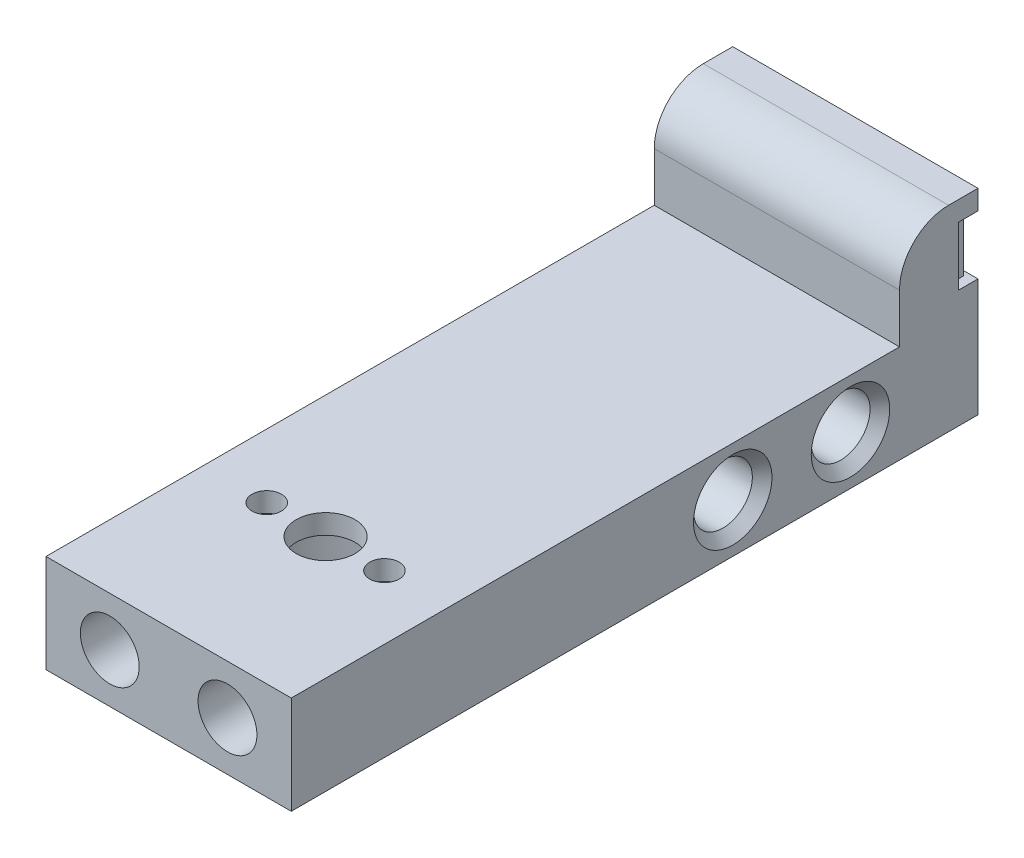
SolidWorks part; units mm, degrees
ref_plane "Front Plane" through (0, 0, 0) normal (0, 0, 1) x (1, 0, 0)
ref_plane "Top Plane" through (0, 0, 0) normal (0, 1, 0) x (1, 0, 0)
ref_plane "Right Plane" through (0, 0, 0) normal (1, 0, 0) x (0, 0, -1)
sketch "Sketch1" plane through (0, 0, 0) normal (0, 1, 0) x (1, 0, 0)
  line L1 (-12.5, 11) -> (12.5, 11)
  line L2 (-12.5, 11) -> (-12.5, -11)
  line L3 (-12.5, -11) -> (12.5, -11)
  line L4 (12.5, 11) -> (12.5, -11)
  line L5 (-12.5, 11) -> (12.5, -11) construction
  line L6 (-12.5, -11) -> (12.5, 11) construction
  point P0 (0, 0)
  dimension "D1" = 22
  dimension "D2" = 25
extrude "Boss-Extrude1" add sketch "Sketch1" along normal blind 10
sketch "Sketch2" plane through (12.5, 0, 0) normal (1, 0, 0) x (0, 0, -1)
  line L0 (-11, 10) -> (-11, 0) construction
  line L1 (-11, 0) -> (11, 0) construction
  line L2 (11, 10) -> (11, 0) construction
  circle A0 centre (-6, 5) radius 3
  circle A1 centre (6, 5) radius 3
  dimension "D1" = 5
  dimension "D3" = 5
  dimension "D2" = 5
extrude "Cut-Extrude1" cut sketch "Sketch2" against normal through all
chamfer "Chamfer1" distance 1 angle 45 4 edges at (-12.5, 5, -9) (-12.5, 5, 3) (12.5, 5, -9) (12.5, 5, 3)
sketch "Sketch3" plane through (0, 10, 0) normal (0, 1, 0) x (1, 0, 0)
  line L6 (-12.5, 11) -> (-12.5, 19)
  line L7 (-12.5, 19) -> (12.5, 19)
  line L8 (12.5, 19) -> (12.5, 11)
  line L9 (12.5, 11) -> (-12.5, 11)
  dimension "D2" = 8
extrude "Boss-Extrude4" add sketch "Sketch3" along normal blind 10 and the other way blind 10
sketch "Sketch5" plane through (0, 0, 11) normal (0, 0, 1) x (1, 0, 0)
  line L1 (-12.5, 10) -> (12.5, 10)
  line L2 (-12.5, 10) -> (-12.5, 0)
  line L3 (-12.5, 0) -> (12.5, 0)
  line L4 (12.5, 10) -> (12.5, 0)
ref_plane "Plane1" through (0, 18, 0) normal (0, 1, 0) x (1, 0, 0)
sketch "Sketch10" plane through (0, 18, 0) normal (0, 1, 0) x (1, 0, 0)
  line L0 (71.7878, 3.2338) -> (71.7878, 1.2338)
  line L1 (96.7878, 1.2338) -> (96.7878, 3.2338)
  line L2 (96.7878, 3.2338) -> (71.7878, 3.2338)
  line L3 (96.7878, 1.2338) -> (71.7878, 1.2338)
  line L4 (95.7878, 1.2338) -> (95.7878, 2.7338)
  line L5 (71.7878, 2.7338) -> (96.7878, 2.7338)
  line L6 (94.7878, 1.2338) -> (94.7878, 2.7338)
  line L7 (93.7878, 1.2338) -> (93.7878, 2.7338)
  line L8 (91.7878, 1.2338) -> (91.7878, 2.7338)
  line L9 (92.7878, 1.2338) -> (92.7878, 2.7338)
  line L10 (90.7878, 1.2338) -> (90.7878, 2.7338)
  line L11 (89.7878, 1.2338) -> (89.7878, 2.7338)
  line L12 (87.7878, 1.2338) -> (87.7878, 2.7338)
  line L13 (88.7878, 1.2338) -> (88.7878, 2.7338)
  line L14 (79.7878, 1.2338) -> (79.7878, 2.7338)
  line L15 (80.7878, 1.2338) -> (80.7878, 2.7338)
  line L16 (81.7878, 1.2338) -> (81.7878, 2.7338)
  line L17 (82.7878, 1.2338) -> (82.7878, 2.7338)
  line L18 (84.7878, 1.2338) -> (84.7878, 2.7338)
  line L19 (83.7878, 1.2338) -> (83.7878, 2.7338)
  line L20 (85.7878, 1.2338) -> (85.7878, 2.7338)
  line L21 (86.7878, 1.2338) -> (86.7878, 2.7338)
  line L22 (74.7878, 1.2338) -> (74.7878, 2.7338)
  line L23 (75.7878, 1.2338) -> (75.7878, 2.7338)
  line L24 (76.7878, 1.2338) -> (76.7878, 2.7338)
  line L25 (77.7878, 1.2338) -> (77.7878, 2.7338)
  line L26 (78.7878, 1.2338) -> (78.7878, 2.7338)
  line L27 (72.7878, 1.2338) -> (72.7878, 2.7338)
  line L28 (73.7878, 1.2338) -> (73.7878, 2.7338)
  line L29 (61.2878, 1) -> (61.2878, -1)
  line L30 (86.2878, -1) -> (86.2878, 1)
  line L31 (86.2878, 1) -> (61.2878, 1)
  line L32 (86.2878, -1) -> (61.2878, -1)
  line L33 (85.2878, -1) -> (85.2878, 0.5)
  line L34 (61.2878, 0.5) -> (86.2878, 0.5)
  line L35 (84.2878, -1) -> (84.2878, 0.5)
  line L36 (83.2878, -1) -> (83.2878, 0.5)
  line L37 (81.2878, -1) -> (81.2878, 0.5)
  line L38 (82.2878, -1) -> (82.2878, 0.5)
  line L39 (80.2878, -1) -> (80.2878, 0.5)
  line L40 (79.2878, -1) -> (79.2878, 0.5)
  line L41 (77.2878, -1) -> (77.2878, 0.5)
  line L42 (78.2878, -1) -> (78.2878, 0.5)
  line L43 (69.2878, -1) -> (69.2878, 0.5)
  line L44 (70.2878, -1) -> (70.2878, 0.5)
  line L45 (71.2878, -1) -> (71.2878, 0.5)
  line L46 (72.2878, -1) -> (72.2878, 0.5)
  line L47 (74.2878, -1) -> (74.2878, 0.5)
  line L48 (73.2878, -1) -> (73.2878, 0.5)
  line L49 (75.2878, -1) -> (75.2878, 0.5)
  line L50 (76.2878, -1) -> (76.2878, 0.5)
  line L51 (64.2878, -1) -> (64.2878, 0.5)
  line L52 (65.2878, -1) -> (65.2878, 0.5)
  line L53 (66.2878, -1) -> (66.2878, 0.5)
  line L54 (67.2878, -1) -> (67.2878, 0.5)
  line L55 (68.2878, -1) -> (68.2878, 0.5)
  line L56 (62.2878, -1) -> (62.2878, 0.5)
  line L57 (63.2878, -1) -> (63.2878, 0.5)
  line L58 (56.698, 4.024) -> (56.698, 2.024)
  line L59 (81.698, 2.024) -> (81.698, 4.024)
  line L60 (81.698, 4.024) -> (56.698, 4.024)
  line L61 (81.698, 2.024) -> (56.698, 2.024)
  line L62 (80.698, 2.024) -> (80.698, 3.524)
  line L63 (56.698, 3.524) -> (81.698, 3.524)
  line L64 (79.698, 2.024) -> (79.698, 3.524)
  line L65 (78.698, 2.024) -> (78.698, 3.524)
  line L66 (76.698, 2.024) -> (76.698, 3.524)
  line L67 (77.698, 2.024) -> (77.698, 3.524)
  line L68 (75.698, 2.024) -> (75.698, 3.524)
  line L69 (74.698, 2.024) -> (74.698, 3.524)
  line L70 (72.698, 2.024) -> (72.698, 3.524)
  line L71 (73.698, 2.024) -> (73.698, 3.524)
  line L72 (64.698, 2.024) -> (64.698, 3.524)
  line L73 (65.698, 2.024) -> (65.698, 3.524)
  line L74 (66.698, 2.024) -> (66.698, 3.524)
  line L75 (67.698, 2.024) -> (67.698, 3.524)
  line L76 (69.698, 2.024) -> (69.698, 3.524)
  line L77 (68.698, 2.024) -> (68.698, 3.524)
  line L78 (70.698, 2.024) -> (70.698, 3.524)
  line L79 (71.698, 2.024) -> (71.698, 3.524)
  line L80 (59.698, 2.024) -> (59.698, 3.524)
  line L81 (60.698, 2.024) -> (60.698, 3.524)
  line L82 (61.698, 2.024) -> (61.698, 3.524)
  line L83 (62.698, 2.024) -> (62.698, 3.524)
  line L84 (63.698, 2.024) -> (63.698, 3.524)
  line L85 (57.698, 2.024) -> (57.698, 3.524)
  line L86 (58.698, 2.024) -> (58.698, 3.524)
  line L87 (58.6901, 3.8366) -> (58.6901, 1.8366)
  line L88 (83.6901, 1.8366) -> (83.6901, 3.8366)
  line L89 (83.6901, 3.8366) -> (58.6901, 3.8366)
  line L90 (83.6901, 1.8366) -> (58.6901, 1.8366)
  line L91 (82.6901, 1.8366) -> (82.6901, 3.3366)
  line L92 (58.6901, 3.3366) -> (83.6901, 3.3366)
  line L93 (81.6901, 1.8366) -> (81.6901, 3.3366)
  line L94 (80.6901, 1.8366) -> (80.6901, 3.3366)
  line L95 (78.6901, 1.8366) -> (78.6901, 3.3366)
  line L96 (79.6901, 1.8366) -> (79.6901, 3.3366)
  line L97 (77.6901, 1.8366) -> (77.6901, 3.3366)
  line L98 (76.6901, 1.8366) -> (76.6901, 3.3366)
  line L99 (74.6901, 1.8366) -> (74.6901, 3.3366)
  line L100 (75.6901, 1.8366) -> (75.6901, 3.3366)
  line L101 (66.6901, 1.8366) -> (66.6901, 3.3366)
  line L102 (67.6901, 1.8366) -> (67.6901, 3.3366)
  line L103 (68.6901, 1.8366) -> (68.6901, 3.3366)
  line L104 (69.6901, 1.8366) -> (69.6901, 3.3366)
  line L105 (71.6901, 1.8366) -> (71.6901, 3.3366)
  line L106 (70.6901, 1.8366) -> (70.6901, 3.3366)
  line L107 (72.6901, 1.8366) -> (72.6901, 3.3366)
  line L108 (73.6901, 1.8366) -> (73.6901, 3.3366)
  line L109 (61.6901, 1.8366) -> (61.6901, 3.3366)
  line L110 (62.6901, 1.8366) -> (62.6901, 3.3366)
  line L111 (63.6901, 1.8366) -> (63.6901, 3.3366)
  line L112 (64.6901, 1.8366) -> (64.6901, 3.3366)
  line L113 (65.6901, 1.8366) -> (65.6901, 3.3366)
  line L114 (59.6901, 1.8366) -> (59.6901, 3.3366)
  line L115 (60.6901, 1.8366) -> (60.6901, 3.3366)
  line L116 (48.1901, 1) -> (48.1901, -1)
  line L117 (73.1901, -1) -> (73.1901, 1)
  line L118 (73.1901, 1) -> (48.1901, 1)
  line L119 (73.1901, -1) -> (48.1901, -1)
  line L120 (72.1901, -1) -> (72.1901, 0.5)
  line L121 (48.1901, 0.5) -> (73.1901, 0.5)
  line L122 (71.1901, -1) -> (71.1901, 0.5)
  line L123 (70.1901, -1) -> (70.1901, 0.5)
  line L124 (68.1901, -1) -> (68.1901, 0.5)
  line L125 (69.1901, -1) -> (69.1901, 0.5)
  line L126 (67.1901, -1) -> (67.1901, 0.5)
  line L127 (66.1901, -1) -> (66.1901, 0.5)
  line L128 (64.1901, -1) -> (64.1901, 0.5)
  line L129 (65.1901, -1) -> (65.1901, 0.5)
  line L130 (56.1901, -1) -> (56.1901, 0.5)
  line L131 (57.1901, -1) -> (57.1901, 0.5)
  line L132 (58.1901, -1) -> (58.1901, 0.5)
  line L133 (59.1901, -1) -> (59.1901, 0.5)
  line L134 (61.1901, -1) -> (61.1901, 0.5)
  line L135 (60.1901, -1) -> (60.1901, 0.5)
  line L136 (62.1901, -1) -> (62.1901, 0.5)
  line L137 (63.1901, -1) -> (63.1901, 0.5)
  line L138 (51.1901, -1) -> (51.1901, 0.5)
  line L139 (52.1901, -1) -> (52.1901, 0.5)
  line L140 (53.1901, -1) -> (53.1901, 0.5)
  line L141 (54.1901, -1) -> (54.1901, 0.5)
  line L142 (55.1901, -1) -> (55.1901, 0.5)
  line L143 (49.1901, -1) -> (49.1901, 0.5)
  line L144 (50.1901, -1) -> (50.1901, 0.5)
  line L145 (-12.5, 19) -> (-12.5, 11) construction
  line L146 (12.5, 11) -> (12.5, 19) construction
  line L147 (12.5, 19) -> (-12.5, 19) construction
  line L148 (-12.5, 19) -> (-12.5, 11)
  line L149 (12.5, 11) -> (12.5, 19)
  line L150 (12.5, 19) -> (-12.5, 19)
  line L151 (12.5, 18.5) -> (-12.5, 18.5)
  line L152 (-12.5, 17) -> (12.5, 17)
  line L153 (11.5, 18.5) -> (11.5, 17)
  line L154 (10.5, 18.5) -> (10.5, 17)
  line L155 (9.5, 18.5) -> (9.5, 17)
  line L156 (8.5, 18.5) -> (8.5, 17)
  line L157 (7.5, 18.5) -> (7.5, 17)
  line L158 (6.5, 18.5) -> (6.5, 17)
  line L159 (5.5, 18.5) -> (5.5, 17)
  line L160 (4.5, 18.5) -> (4.5, 17)
  line L161 (3.5, 18.5) -> (3.5, 17)
  line L162 (2.5, 18.5) -> (2.5, 17)
  line L163 (1.5, 18.5) -> (1.5, 17)
  line L164 (0.5, 18.5) -> (0.5, 17)
  line L165 (-0.5, 18.5) -> (-0.5, 17)
  line L166 (-1.5, 18.5) -> (-1.5, 17)
  line L167 (-2.5, 18.5) -> (-2.5, 17)
  line L168 (-3.5, 18.5) -> (-3.5, 17)
  line L169 (-4.5, 18.5) -> (-4.5, 17)
  line L170 (-11.5, 18.5) -> (-11.5, 17)
  line L171 (-10.5, 18.5) -> (-10.5, 17)
  line L172 (-9.5, 18.5) -> (-9.5, 17)
  line L173 (-8.5, 18.5) -> (-8.5, 17)
  line L174 (-7.5, 18.5) -> (-7.5, 17)
  line L175 (-6.5, 18.5) -> (-6.5, 17)
  line L176 (-5.5, 18.5) -> (-5.5, 17)
  dimension "D1" = 0.5
  dimension "D2" = 2
  dimension "D3" = 1
  dimension "D4" = 1
  dimension "D5" = 1
extrude "Cut-Extrude6" cut sketch "Sketch10" against normal blind 6 contours L151 L153 L152 L149 | L151 L155 L152 L154 | L151 L149 L150 L148 | L151 L157 L152 L156 | L151 L159 L152 L158 | L151 L161 L152 L160 | L151 L163 L152 L162 | L151 L165 L152 L164 | L151 L167 L152 L166 | L151 L169 L152 L168 | L176 L151 L175 L152 | L174 L151 L173 L152 | L172 L151 L171 L152 | L170 L151 L148 L152 region at (0, 18, -18.75) region at (-12, 18, -17.75) region at (12, 18, -17.75) region at (-10, 18, -17.75) region at (10, 18, -17.75) region at (-8, 18, -17.75) region at (8, 18, -17.75) region at (-6, 18, -17.75) region at (6, 18, -17.75) region at (-4, 18, -17.75) region at (4, 18, -17.75) region at (-2, 18, -17.75) region at (2, 18, -17.75) region at (0, 18, -17.75)
extrude "Boss-Extrude3" add sketch "Sketch5" along normal blind 40
sketch "Sketch6" plane through (0, 0, 0) normal (0, -1, 0) x (1, 0, 0)
  circle A0 centre (0, 35) radius 11
  dimension "D1" = 35
  dimension "D2" = 22
extrude "Cut-Extrude3" cut sketch "Sketch6" against normal blind 8
sketch "Sketch7" plane through (0, 8, 0) normal (0, -1, 0) x (1, 0, 0)
  circle A0 centre (0, 35) radius 3
  circle A5 centre (-6, 35) radius 1.5
  circle A6 centre (6, 35) radius 1.5
  dimension "D1" = 6
  dimension "D2" = 6
extrude "Cut-Extrude4" cut sketch "Sketch7" against normal blind 8
sketch "Sketch8" plane through (0, 0, 51) normal (0, 0, 1) x (1, 0, 0)
  line L0 (-12.5, 0) -> (12.5, 0) construction
  line L1 (12.5, 0) -> (12.5, 10) construction
  line L2 (-12.5, 10) -> (-12.5, 0) construction
  circle A0 centre (6, 5) radius 3
  circle A1 centre (-6, 5) radius 3
  dimension "D1" = 5
  dimension "D3" = 6.5
  dimension "D2" = 6.5
extrude "Cut-Extrude5" cut sketch "Sketch8" against normal blind 5
fillet "Fillet1" radius 5 1 edges at (0, 20, -11)
